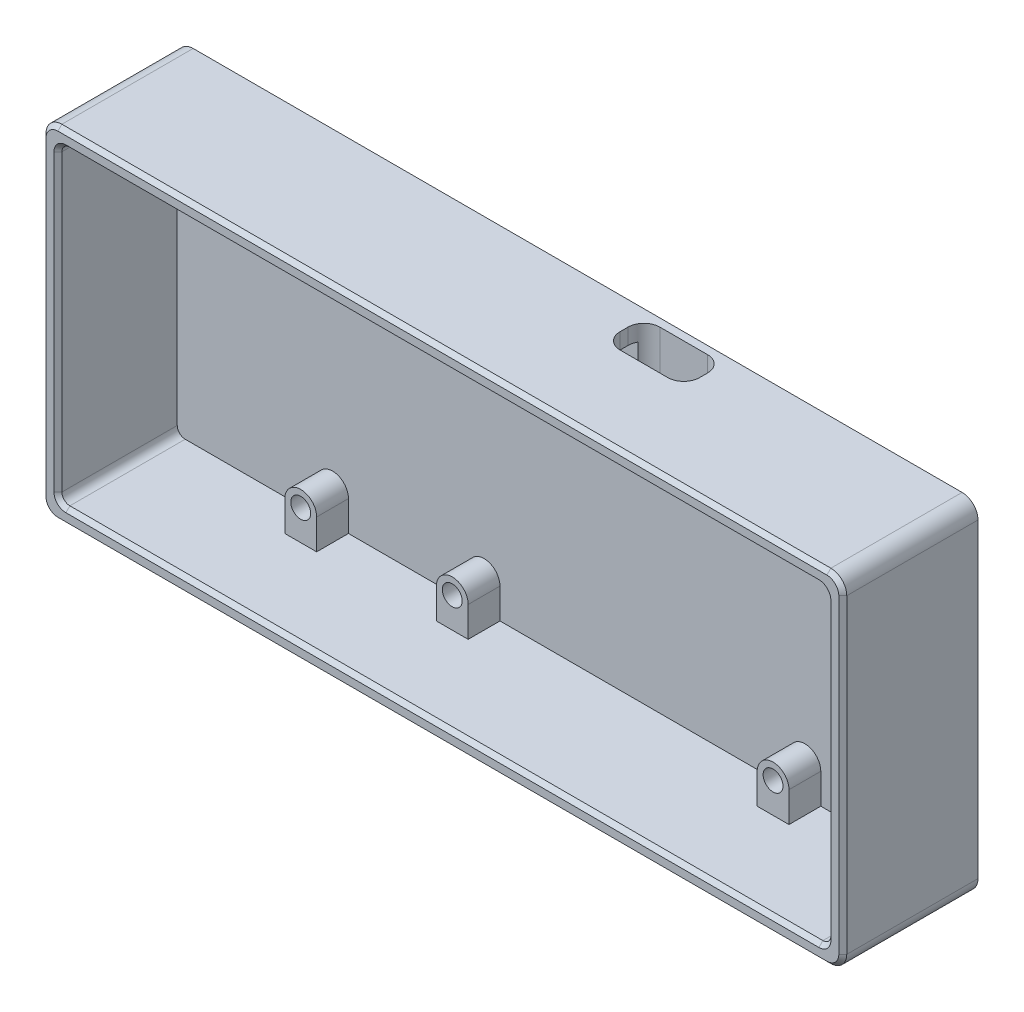
SolidWorks part; units mm, degrees
ref_plane "前视基准面" through (0, 0, 0) normal (0, 0, 1) x (1, 0, 0)
ref_plane "上视基准面" through (0, 0, 0) normal (0, 1, 0) x (1, 0, 0)
ref_plane "右视基准面" through (0, 0, 0) normal (1, 0, 0) x (0, 0, -1)
sketch "草图1" plane through (0, 0, 0) normal (0, 0, 1) x (1, 0, 0)
  line L2 (2.2254, 43.5224) -> (2.2254, 4.4743)
  line L3 (4.2254, 2.4743) -> (100.9001, 2.4743)
  line L4 (100.9001, 45.5224) -> (4.2254, 45.5224)
  line L5 (102.9001, 43.5224) -> (102.9001, 4.4743)
  line L6 (4.2254, 2.4743) -> (6.2254, 2.4743)
  line L7 (4.2252, 42.5233) -> (4.2259, 5.4743)
  line L8 (100.9003, 42.5234) -> (100.8996, 5.4743)
  line L9 (21.7509, 8.2734) -> (21.7509, 4.4743)
  line L10 (25.7509, 8.2727) -> (25.7509, 4.4743)
  line L11 (40.8008, 8.2727) -> (40.8008, 4.4743)
  line L12 (44.8008, 8.272) -> (44.8008, 4.4743)
  line L13 (81.1358, 8.2734) -> (81.1358, 4.4743)
  line L14 (85.1358, 8.2727) -> (85.1358, 4.4743)
  line L15 (21.7509, 39.7233) -> (21.7509, 43.5234)
  line L16 (25.7509, 39.7226) -> (25.7509, 43.5234)
  line L17 (40.8008, 39.7226) -> (40.8008, 43.5234)
  line L18 (44.8008, 39.7219) -> (44.8008, 43.5234)
  line L19 (81.1358, 39.7226) -> (81.1358, 43.5227)
  line L20 (85.1358, 39.7219) -> (85.1358, 43.5227)
  line L21 (5.2259, 4.4743) -> (21.7509, 4.4743)
  line L22 (21.7509, 4.4743) -> (25.7509, 4.4743)
  line L23 (25.7509, 4.4743) -> (40.8008, 4.4743)
  line L24 (40.8008, 4.4743) -> (44.8008, 4.4743)
  line L25 (44.8008, 4.4743) -> (81.1358, 4.4743)
  line L26 (81.1358, 4.4743) -> (85.1358, 4.4743)
  line L27 (85.1358, 4.4743) -> (99.8996, 4.4743)
  line L28 (99.9003, 43.5234) -> (85.1358, 43.5227)
  line L29 (85.1358, 43.5227) -> (81.1358, 43.5227)
  line L30 (81.1358, 43.5227) -> (44.8008, 43.5234)
  line L31 (44.8008, 43.5234) -> (40.8008, 43.5234)
  line L32 (40.8008, 43.5234) -> (25.7509, 43.5234)
  line L33 (25.7509, 43.5234) -> (21.7509, 43.5234)
  line L34 (21.7509, 43.5234) -> (5.2252, 43.5234)
  line L35 (71.9001, 43.5234) -> (61.9001, 43.5234)
  line L36 (71.9001, 43.5234) -> (71.9001, 33.5234)
  line L37 (71.9001, 33.5234) -> (61.9001, 33.5234)
  line L38 (61.9001, 33.5234) -> (61.9001, 43.5234)
  arc A0 (4.2254, 45.5224) -> (2.2254, 43.5224) centre (4.2254, 43.5224) ccw
  arc A1 (102.9001, 43.5224) -> (100.9001, 45.5224) centre (100.9001, 43.5224) ccw
  arc A2 (100.9001, 2.4743) -> (102.9001, 4.4743) centre (100.9001, 4.4743) ccw
  arc A3 (2.2254, 4.4743) -> (4.2254, 2.4743) centre (4.2254, 4.4743) ccw
  arc A4 (5.2252, 43.5234) -> (4.2252, 42.5233) centre (5.2252, 42.5234) ccw
  arc A5 (4.2259, 5.4743) -> (5.2259, 4.4743) centre (5.2259, 5.4743) ccw
  arc A6 (100.9003, 42.5234) -> (99.9003, 43.5234) centre (99.9003, 42.5234) ccw
  arc A7 (99.8996, 4.4743) -> (100.8996, 5.4743) centre (99.8996, 5.4743) ccw
  circle A8 centre (23.7509, 39.7226) radius 1.25
  circle A9 centre (42.8008, 39.7219) radius 1.25
  circle A10 centre (83.1358, 39.7219) radius 1.25
  circle A11 centre (23.7509, 8.2734) radius 1.25
  circle A12 centre (42.8008, 8.2727) radius 1.25
  circle A13 centre (83.1358, 8.2734) radius 1.25
  arc A14 (21.7509, 39.7233) -> (25.7509, 39.7226) centre (23.7509, 39.7226) ccw
  arc A15 (40.8008, 39.7226) -> (44.8008, 39.7219) centre (42.8008, 39.7219) ccw
  arc A16 (81.1358, 39.7226) -> (85.1358, 39.7219) centre (83.1358, 39.7219) ccw
  arc A17 (44.8008, 8.272) -> (40.8008, 8.2727) centre (42.8008, 8.2727) ccw
  arc A18 (25.7509, 8.2727) -> (21.7509, 8.2734) centre (23.7509, 8.2734) ccw
  arc A19 (85.1358, 8.2727) -> (81.1358, 8.2734) centre (83.1358, 8.2734) ccw
extrude "凸台-拉伸1" add sketch "草图1" along normal blind 2 contours L3 A2 L5 A1 L4 A0 L2 A3
sketch "草图2" plane through (0, 0, 2) normal (0, 0, 1) x (1, 0, 0)
  line L0 (61.9001, 33.5234) -> (61.9001, 43.5234) construction
  line L1 (71.9001, 33.5234) -> (61.9001, 33.5234) construction
  line L2 (71.9001, 43.5234) -> (71.9001, 33.5234) construction
  line L3 (61.9001, 33.5234) -> (61.9001, 43.5234)
  line L4 (71.9001, 33.5234) -> (61.9001, 33.5234)
  line L5 (71.9001, 43.5234) -> (71.9001, 33.5234)
  line L6 (61.9001, 43.5234) -> (71.9001, 43.5234)
extrude "切除-拉伸1" cut sketch "草图2" against normal blind 1
sketch "草图3" plane through (0, 0, 2) normal (0, 0, 1) x (1, 0, 0)
  line L0 (100.9001, 45.5224) -> (4.2254, 45.5224) construction
  line L1 (2.2254, 43.5224) -> (2.2254, 4.4743) construction
  line L2 (4.2254, 2.4743) -> (100.9001, 2.4743) construction
  line L3 (102.9001, 43.5224) -> (102.9001, 4.4743) construction
  line L4 (99.9003, 43.5234) -> (85.1358, 43.5227) construction
  line L5 (85.1358, 43.5227) -> (81.1358, 43.5227) construction
  line L6 (81.1358, 43.5227) -> (44.8008, 43.5234) construction
  line L7 (44.8008, 43.5234) -> (40.8008, 43.5234) construction
  line L8 (40.8008, 43.5234) -> (25.7509, 43.5234) construction
  line L9 (25.7509, 43.5234) -> (21.7509, 43.5234) construction
  line L10 (21.7509, 43.5234) -> (5.2252, 43.5234) construction
  line L11 (4.2252, 42.5233) -> (4.2259, 5.4743) construction
  line L12 (5.2259, 4.4743) -> (21.7509, 4.4743) construction
  line L13 (21.7509, 4.4743) -> (25.7509, 4.4743) construction
  line L14 (25.7509, 4.4743) -> (40.8008, 4.4743) construction
  line L15 (40.8008, 4.4743) -> (44.8008, 4.4743) construction
  line L16 (44.8008, 4.4743) -> (81.1358, 4.4743) construction
  line L17 (81.1358, 4.4743) -> (85.1358, 4.4743) construction
  line L18 (85.1358, 4.4743) -> (99.8996, 4.4743) construction
  line L19 (100.9003, 42.5234) -> (100.8996, 5.4743) construction
  line L20 (100.9001, 45.5224) -> (4.2254, 45.5224)
  line L21 (2.2254, 43.5224) -> (2.2254, 4.4743)
  line L22 (4.2254, 2.4743) -> (100.9001, 2.4743)
  line L23 (102.9001, 43.5224) -> (102.9001, 4.4743)
  line L24 (99.9003, 43.5234) -> (85.1358, 43.5227)
  line L25 (85.1358, 43.5227) -> (81.1358, 43.5227)
  line L26 (81.1358, 43.5227) -> (44.8008, 43.5234)
  line L27 (44.8008, 43.5234) -> (40.8008, 43.5234)
  line L28 (40.8008, 43.5234) -> (25.7509, 43.5234)
  line L29 (25.7509, 43.5234) -> (21.7509, 43.5234)
  line L30 (21.7509, 43.5234) -> (5.2252, 43.5234)
  line L31 (4.2252, 42.5233) -> (4.2259, 5.4743)
  line L32 (5.2259, 4.4743) -> (21.7509, 4.4743)
  line L33 (21.7509, 4.4743) -> (25.7509, 4.4743)
  line L34 (25.7509, 4.4743) -> (40.8008, 4.4743)
  line L35 (40.8008, 4.4743) -> (44.8008, 4.4743)
  line L36 (44.8008, 4.4743) -> (81.1358, 4.4743)
  line L37 (81.1358, 4.4743) -> (85.1358, 4.4743)
  line L38 (85.1358, 4.4743) -> (99.8996, 4.4743)
  line L39 (100.9003, 42.5234) -> (100.8996, 5.4743)
  arc A0 (4.2254, 45.5224) -> (2.2254, 43.5224) centre (4.2254, 43.5224) ccw construction
  arc A1 (2.2254, 4.4743) -> (4.2254, 2.4743) centre (4.2254, 4.4743) ccw construction
  arc A2 (100.9001, 2.4743) -> (102.9001, 4.4743) centre (100.9001, 4.4743) ccw construction
  arc A3 (102.9001, 43.5224) -> (100.9001, 45.5224) centre (100.9001, 43.5224) ccw construction
  arc A4 (99.8996, 4.4743) -> (100.8996, 5.4743) centre (99.8996, 5.4743) ccw construction
  arc A5 (100.9003, 42.5234) -> (99.9003, 43.5234) centre (99.9003, 42.5234) ccw construction
  arc A6 (5.2252, 43.5234) -> (4.2252, 42.5233) centre (5.2252, 42.5234) ccw construction
  arc A7 (4.2259, 5.4743) -> (5.2259, 4.4743) centre (5.2259, 5.4743) ccw construction
  arc A8 (4.2254, 45.5224) -> (2.2254, 43.5224) centre (4.2254, 43.5224) ccw
  arc A9 (2.2254, 4.4743) -> (4.2254, 2.4743) centre (4.2254, 4.4743) ccw
  arc A10 (100.9001, 2.4743) -> (102.9001, 4.4743) centre (100.9001, 4.4743) ccw
  arc A11 (102.9001, 43.5224) -> (100.9001, 45.5224) centre (100.9001, 43.5224) ccw
  arc A12 (99.8996, 4.4743) -> (100.8996, 5.4743) centre (99.8996, 5.4743) ccw
  arc A13 (100.9003, 42.5234) -> (99.9003, 43.5234) centre (99.9003, 42.5234) ccw
  arc A14 (5.2252, 43.5234) -> (4.2252, 42.5233) centre (5.2252, 42.5234) ccw
  arc A15 (4.2259, 5.4743) -> (5.2259, 4.4743) centre (5.2259, 5.4743) ccw
extrude "凸台-拉伸2" add sketch "草图3" along normal blind 15
sketch "草图4" plane through (0, 0, 2) normal (0, 0, 1) x (1, 0, 0)
  line L0 (21.7509, 39.7233) -> (21.7509, 43.5234) construction
  line L1 (25.7509, 43.5234) -> (21.7509, 43.5234) construction
  line L2 (25.7509, 39.7226) -> (25.7509, 43.5234) construction
  line L3 (40.8008, 39.7226) -> (40.8008, 43.5234) construction
  line L4 (44.8008, 43.5234) -> (40.8008, 43.5234) construction
  line L5 (44.8008, 39.7219) -> (44.8008, 43.5234) construction
  line L6 (81.1358, 39.7226) -> (81.1358, 43.5227) construction
  line L7 (85.1358, 43.5227) -> (81.1358, 43.5227) construction
  line L8 (85.1358, 39.7219) -> (85.1358, 43.5227) construction
  line L9 (21.7509, 8.2734) -> (21.7509, 4.4743) construction
  line L10 (21.7509, 4.4743) -> (25.7509, 4.4743) construction
  line L11 (25.7509, 8.2727) -> (25.7509, 4.4743) construction
  line L12 (40.8008, 8.2727) -> (40.8008, 4.4743) construction
  line L13 (40.8008, 4.4743) -> (44.8008, 4.4743) construction
  line L14 (44.8008, 8.272) -> (44.8008, 4.4743) construction
  line L15 (81.1358, 8.2734) -> (81.1358, 4.4743) construction
  line L16 (85.1358, 8.2727) -> (85.1358, 4.4743) construction
  line L17 (81.1358, 4.4743) -> (85.1358, 4.4743) construction
  line L18 (21.7509, 39.7233) -> (21.7509, 43.5234)
  line L19 (25.7509, 43.5234) -> (21.7509, 43.5234)
  line L20 (25.7509, 39.7226) -> (25.7509, 43.5234)
  line L21 (40.8008, 39.7226) -> (40.8008, 43.5234)
  line L22 (44.8008, 43.5234) -> (40.8008, 43.5234)
  line L23 (44.8008, 39.7219) -> (44.8008, 43.5234)
  line L24 (81.1358, 39.7226) -> (81.1358, 43.5227)
  line L25 (85.1358, 43.5227) -> (81.1358, 43.5227)
  line L26 (85.1358, 39.7219) -> (85.1358, 43.5227)
  line L27 (21.7509, 8.2734) -> (21.7509, 4.4743)
  line L28 (21.7509, 4.4743) -> (25.7509, 4.4743)
  line L29 (25.7509, 8.2727) -> (25.7509, 4.4743)
  line L30 (40.8008, 8.2727) -> (40.8008, 4.4743)
  line L31 (40.8008, 4.4743) -> (44.8008, 4.4743)
  line L32 (44.8008, 8.272) -> (44.8008, 4.4743)
  line L33 (81.1358, 8.2734) -> (81.1358, 4.4743)
  line L34 (85.1358, 8.2727) -> (85.1358, 4.4743)
  line L35 (81.1358, 4.4743) -> (85.1358, 4.4743)
  arc A0 (21.7509, 39.7233) -> (25.7509, 39.7226) centre (23.7509, 39.7226) ccw construction
  arc A1 (40.8008, 39.7226) -> (44.8008, 39.7219) centre (42.8008, 39.7219) ccw construction
  arc A2 (81.1358, 39.7226) -> (85.1358, 39.7219) centre (83.1358, 39.7219) ccw construction
  arc A3 (25.7509, 8.2727) -> (21.7509, 8.2734) centre (23.7509, 8.2734) ccw construction
  arc A4 (44.8008, 8.272) -> (40.8008, 8.2727) centre (42.8008, 8.2727) ccw construction
  arc A5 (85.1358, 8.2727) -> (81.1358, 8.2734) centre (83.1358, 8.2734) ccw construction
  arc A6 (21.7509, 39.7233) -> (25.7509, 39.7226) centre (23.7509, 39.7226) ccw
  arc A7 (40.8008, 39.7226) -> (44.8008, 39.7219) centre (42.8008, 39.7219) ccw
  arc A8 (81.1358, 39.7226) -> (85.1358, 39.7219) centre (83.1358, 39.7219) ccw
  arc A9 (25.7509, 8.2727) -> (21.7509, 8.2734) centre (23.7509, 8.2734) ccw
  arc A10 (44.8008, 8.272) -> (40.8008, 8.2727) centre (42.8008, 8.2727) ccw
  arc A11 (85.1358, 8.2727) -> (81.1358, 8.2734) centre (83.1358, 8.2734) ccw
extrude "凸台-拉伸3" add sketch "草图4" along normal blind 4
sketch "草图5" plane through (0, 0, 6) normal (0, 0, 1) x (1, 0, 0)
  point P0 (23.7509, 39.7226)
  point P1 (42.8008, 39.7219)
  point P3 (83.1358, 39.7219)
  point P5 (83.1358, 8.2734)
  point P7 (42.8008, 8.2727)
  point P9 (23.7509, 8.2734)
hole_wizard "大小mm 暗销孔2" positions "3D草图3" profile "草图8" hole size "Ø2.5" standard "GB"
sketch3d "3D草图3"
  point P0 (23.7509, 39.7226, 6)
  point P3 (42.8008, 39.7219, 6)
  point P6 (83.1358, 39.7219, 6)
  point P9 (83.1358, 8.2734, 6)
  point P12 (42.8008, 8.2727, 6)
  point P15 (23.7509, 8.2734, 6)
sketch "草图8" plane through (23.7509, 39.7226, 6) normal (1, 0, 0) x (0, -1, 0)
  line L0 (0, 0) -> (0, 4.7511)
  line L1 (0, 4.7511) -> (1.25, 4)
  line L2 (1.25, 4) -> (1.25, 0)
  line L5 (1.25, 0) -> (0, 0)
  line L10 (0, 4.7511) -> (-1.25, 4) construction
  line L11 (0, -6.35) -> (0, 107.95) construction
  dimension "孔直径" = 2.5
  dimension "孔深度" = 4
  dimension "导头角度" = 118
sketch "草图9" plane through (0, 45.5224, 0) normal (0, 1, 0) x (1, 0, 0)
  line L0 (61.9001, -1) -> (71.9001, -1)
  line L1 (71.9001, -1) -> (71.9001, -6)
  line L2 (71.9001, -6) -> (61.9001, -6)
  line L3 (61.9001, -6) -> (61.9001, -1)
extrude "切除-拉伸2" cut sketch "草图9" against normal blind 2
fillet "圆角1" radius 2 4 edges at (61.9001, 44.5227, 6) (71.9001, 44.5226, 6) (71.9001, 39.5229, 1) (61.9001, 39.5229, 1)
chamfer "倒角1" distance 0.5 angle 45 19 edges at (83.1358, 43.5227, 17) (62.9683, 43.523, 17) (25.013, 43.5234, 17) (4.5181, 43.2305, 17) (4.2255, 23.9988, 17) (4.5188, 4.7672, 17) (52.5627, 4.4743, 17) (100.6067, 4.7672, 17) (100.9, 23.9988, 17) (100.6074, 43.2305, 17) (92.518, 43.523, 17) (102.9001, 23.9983, 17) (102.3143, 3.0601, 17) (52.5628, 2.4743, 17) (2.8112, 3.0601, 17) (2.2254, 23.9983, 17) (2.8112, 44.9366, 17) (52.5628, 45.5224, 17) (102.3143, 44.9366, 17)
